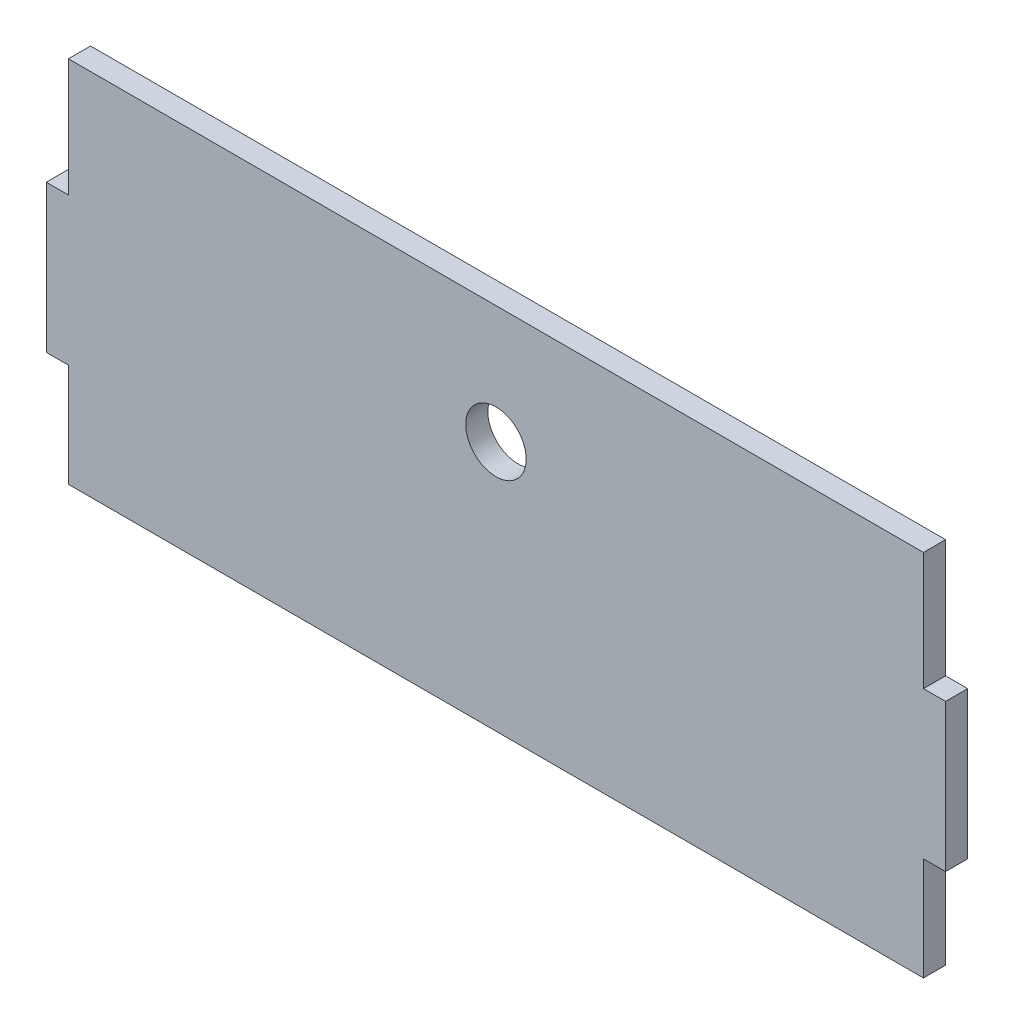
SolidWorks part; units mm, degrees
material "Acrylic (Medium-high impact)"
ref_plane "Front Plane" through (0, 0, 0) normal (0, 0, 1) x (1, 0, 0)
ref_plane "Top Plane" through (0, 0, 0) normal (0, 1, 0) x (1, 0, 0)
ref_plane "Right Plane" through (0, 0, 0) normal (1, 0, 0) x (0, 0, -1)
sketch "Sketch1" plane through (0, 0, 0) normal (0, 0, 1) x (1, 0, 0)
  line L0 (-61, 10) -> (-61, -10)
  line L1 (-61, -10) -> (-58, -10)
  line L2 (-58, -10) -> (-58, -24)
  line L3 (-58, -24) -> (58, -24)
  line L4 (58, -24) -> (58, -10)
  line L5 (58, -10) -> (61, -10)
  line L6 (61, -10) -> (61, 10)
  line L7 (61, 10) -> (58, 10)
  line L8 (58, 10) -> (58, 26)
  line L9 (58, 26) -> (-58, 26)
  line L10 (-58, 26) -> (-58, 10)
  line L11 (-58, 10) -> (-61, 10)
  line L12 (-61, 0) -> (0, 0) construction
  line L13 (0, 0) -> (61, 0) construction
  circle A0 centre (0, 10) radius 4.1
  dimension "D6" = 8.2
  dimension "D1" = 3
  dimension "D2" = 20
  dimension "D3" = 50
  dimension "D4" = 116
  dimension "D5" = 14
extrude "Boss-Extrude1" add sketch "Sketch1" along normal blind 3
